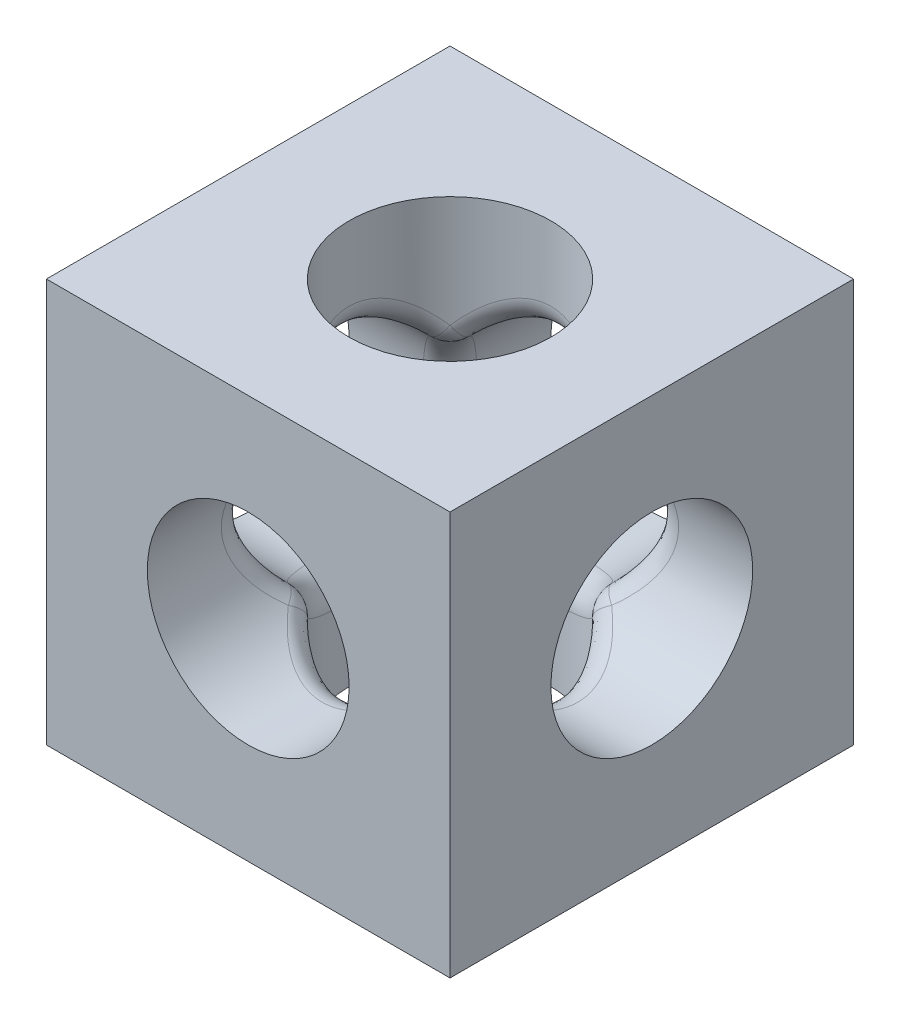
SolidWorks part; units mm, degrees
ref_plane "前视基准面" through (0, 0, 0) normal (0, 0, 1) x (1, 0, 0)
ref_plane "上视基准面" through (0, 0, 0) normal (0, 1, 0) x (1, 0, 0)
ref_plane "右视基准面" through (0, 0, 0) normal (1, 0, 0) x (0, 0, -1)
other "Configuration Table"
sketch "草图1" plane through (0, 0, 0) normal (0, 1, 0) x (1, 0, 0)
  line L0 (3, 0) -> (3, 6) construction
  line L1 (0, 0) -> (6, 0)
  line L2 (0, 0) -> (0, 6)
  line L3 (0, 6) -> (6, 6)
  line L4 (6, 0) -> (6, 6)
  line L6 (0, 3) -> (6, 3) construction
  circle A0 centre (3, 3) radius 1.5
  dimension "D3" = 3
  dimension "D1" = 6
  dimension "D2" = 6
extrude "凸台-拉伸1" add sketch "草图1" along normal blind 6
sketch "草图2" plane through (0, 0, 0) normal (0, 0, 1) x (1, 0, 0)
  line L0 (3, 0) -> (3, 6) construction
  line L1 (0, 0) -> (6, 0) construction
  line L2 (0, 6) -> (6, 6) construction
  line L3 (0, 3) -> (6, 3) construction
  line L4 (0, 6) -> (0, 0) construction
  line L5 (6, 6) -> (6, 0) construction
  circle A0 centre (3, 3) radius 1.5
  dimension "D1" = 3
extrude "切除-拉伸1" cut sketch "草图2" against normal blind 6 contours A0
sketch "草图3" plane through (6, 0, 0) normal (1, 0, 0) x (0, 0, -1)
  line L0 (3, 0) -> (3, 6) construction
  line L1 (0, 0) -> (6, 0) construction
  line L2 (0, 6) -> (6, 6) construction
  line L4 (0, 6) -> (0, 0) construction
  line L5 (0, 3) -> (6, 3) construction
  line L6 (6, 6) -> (6, 0) construction
  circle A0 centre (3, 3) radius 1.5
  dimension "D1" = 3
extrude "切除-拉伸2" cut sketch "草图3" against normal blind 6 contours A0
fillet "圆角1" radius 0.4 12 edges at (3, 1.5, -4.5) (3, 4.5, -4.5) (3, 1.5, -1.5) (3, 4.5, -1.5) (1.5, 4.5, -3) (1.5, 1.5, -3) (4.5, 1.5, -3) (4.5, 4.5, -3) (4.5, 3, -4.5) (1.5, 3, -4.5) (1.5, 3, -1.5) (4.5, 3, -1.5)
